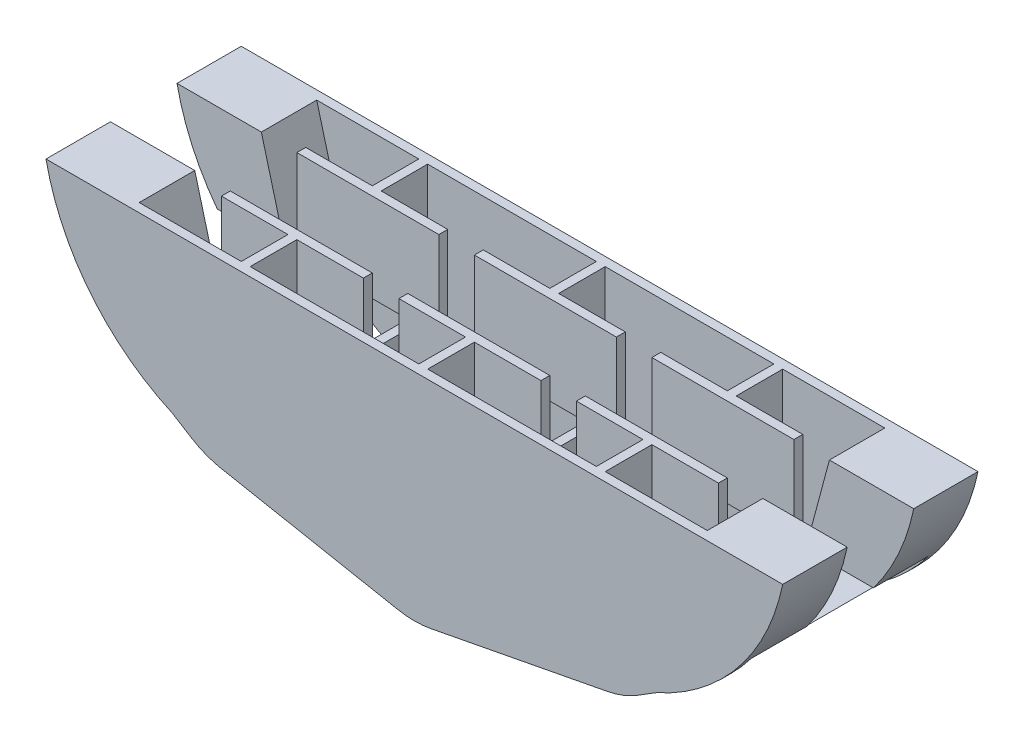
SolidWorks part; units mm, degrees
ref_plane "Front" through (0, 0, 0) normal (0, 0, 1) x (1, 0, 0)
ref_plane "Top" through (0, 0, 0) normal (0, 1, 0) x (1, 0, 0)
ref_plane "Right" through (0, 0, 0) normal (1, 0, 0) x (0, 0, -1)
sketch "Sketch1" plane through (0, 0, 0) normal (0, 0, 1) x (1, 0, 0)
  line L0 (-152.4, 62.23) -> (0, 62.23) construction
  line L1 (-152.4, -62.23) -> (152.4, -62.23) construction
  line L2 (-152.4, -62.23) -> (-152.4, 62.23) construction
  line L3 (-152.4, 62.23) -> (152.4, 62.23) construction
  line L4 (152.4, -62.23) -> (152.4, 62.23) construction
  line L5 (-152.4, -62.23) -> (152.4, 62.23) construction
  line L6 (-152.4, 62.23) -> (152.4, -62.23) construction
  line L7 (-152.4, 62.23) -> (-152.4, -33.02)
  line L8 (-152.4, -33.02) -> (0, -62.23)
  line L9 (0, -62.23) -> (152.4, -32.9764)
  line L10 (152.4, -32.9764) -> (152.4, 62.23)
  line L11 (152.4, 62.23) -> (-152.4, 62.23)
  point P0 (0, 0)
  dimension "D1" = 304.8
  dimension "D2" = 124.46
  dimension "D3" = 95.25
extrude "Boss-Extrude1" add sketch "Sketch1" against normal blind 111.76
ref_plane "Plane1" through (0, 0, -5.08) normal (0, 0, 1) x (1, 0, 0)
sketch "Sketch2" plane through (0, 0, 0) normal (0, 0, 1) x (1, 0, 0)
  line L0 (-152.4, -33.02) -> (-152.4, -13.97) construction
  line L1 (-152.4, 62.23) -> (-152.4, -33.02) construction
  line L2 (152.4, -32.9764) -> (152.4, 62.23) construction
  line L3 (-152.4, -13.97) -> (152.4, -13.97)
  line L4 (-152.4, -13.97) -> (-152.4, 11.43)
  line L5 (-152.4, 11.43) -> (152.4, 11.43)
  line L6 (152.4, -13.97) -> (152.4, 11.43)
  dimension "D1" = 19.05
  dimension "D2" = 25.4
sketch "Sketch5" plane through (0, 0, -5.08) normal (0, 0, 1) x (1, 0, 0)
  line L1 (-152.4, 11.43) -> (152.4, 11.43)
  line L2 (-152.4, 11.43) -> (-152.4, -13.97)
  line L3 (-152.4, -13.97) -> (152.4, -13.97)
  line L4 (152.4, 11.43) -> (152.4, -13.97)
  dimension "D1" = 19.05
  dimension "D2" = 25.4
extrude "Cut-Extrude3" cut sketch "Sketch5" against normal blind 101.6
sketch "Sketch3" plane through (0, 62.23, 0) normal (0, 1, 0) x (1, 0, 0)
  line L0 (152.4, 111.76) -> (-152.4, 111.76) construction
  line L1 (-2.54, 5.08) -> (-99.06, 5.08)
  line L2 (-2.54, 5.08) -> (-2.54, 106.68)
  line L3 (-2.54, 106.68) -> (-99.06, 106.68)
  line L4 (-99.06, 5.08) -> (-99.06, 106.68)
  line L5 (152.4, 0) -> (-152.4, 0) construction
  line L6 (0, 0) -> (0, 111.76) construction
  line L7 (2.54, 106.68) -> (99.06, 106.68)
  line L8 (99.06, 5.08) -> (99.06, 106.68)
  line L9 (2.54, 5.08) -> (99.06, 5.08)
  line L10 (2.54, 5.08) -> (2.54, 106.68)
  line L11 (-152.4, 111.76) -> (-152.4, 0) construction
  line L12 (-104.14, 106.68) -> (-152.4, 106.68)
  line L13 (-104.14, 106.68) -> (-104.14, 5.08)
  line L14 (-104.14, 5.08) -> (-152.4, 5.08)
  line L15 (-152.4, 106.68) -> (-152.4, 5.08)
  line L16 (104.14, 5.08) -> (152.4, 5.08)
  line L17 (152.4, 106.68) -> (152.4, 5.08)
  line L18 (104.14, 106.68) -> (152.4, 106.68)
  line L19 (104.14, 106.68) -> (104.14, 5.08)
  dimension "D1" = 2.54
  dimension "D2" = 96.52
  dimension "D3" = 5.08
  dimension "D4" = 5.08
  dimension "D5" = 5.08
  dimension "D6" = 5.08
  dimension "D7" = 5.08
extrude "Cut-Extrude4" cut sketch "Sketch3" against normal through all both and the other way through all
sketch "Sketch6" plane through (-104.14, 0, 0) normal (-1, 0, 0) x (0, 0, 1)
  line L0 (-5.08, 11.43) -> (-106.68, 11.43) construction
  line L1 (-74.9821, 11.43) -> (-36.8821, 11.43)
  line L2 (-74.9821, 11.43) -> (-74.9821, 62.23)
  line L3 (-74.9821, 62.23) -> (-36.8821, 62.23)
  line L4 (-36.8821, 11.43) -> (-36.8821, 62.23)
  line L5 (-5.08, 62.23) -> (-106.68, 62.23) construction
  dimension "D1" = 38.1
extrude "Cut-Extrude5" cut sketch "Sketch6" against normal up to surface (208.28 mm away) up to face at (104.14, 36.83, -55.88)
ref_plane "Plane2" through (0, 0, -36.8821) normal (0, 0, -1) x (-1, 0, 0)
sketch "Sketch7" plane through (0, 0, -36.8821) normal (0, 0, -1) x (-1, 0, 0)
  line L1 (-40.64, 62.23) -> (40.64, 62.23)
  line L2 (-40.64, 62.23) -> (-40.64, 11.43)
  line L3 (-40.64, 11.43) -> (40.64, 11.43)
  line L4 (40.64, 62.23) -> (40.64, 11.43)
  line L5 (60.96, 62.23) -> (142.24, 62.23)
  line L6 (60.96, 62.23) -> (60.96, 11.43)
  line L7 (60.96, 11.43) -> (142.24, 11.43)
  line L8 (142.24, 62.23) -> (142.24, 11.43)
  line L9 (-142.24, 62.23) -> (-60.96, 62.23)
  line L10 (-142.24, 62.23) -> (-142.24, 11.43)
  line L11 (-142.24, 11.43) -> (-60.96, 11.43)
  line L12 (-60.96, 62.23) -> (-60.96, 11.43)
  dimension "D1" = 38.1
  dimension "D2" = 38.1
  dimension "D3" = 38.1
  dimension "D4" = 38.1
  dimension "D5" = 38.1
  dimension "D6" = 38.1
extrude "Boss-Extrude2" add sketch "Sketch7" against normal blind 5.08
ref_plane "Plane3" through (0, 0, -55.9321) normal (0, 0, -1) x (-1, 0, 0)
mirror "Mirror1" about plane through (0, 0, -55.9321) normal (0, 0, -1) of "Boss-Extrude2"
sketch "Sketch8" plane through (0, 0, 0) normal (0, 0, 1) x (1, 0, 0)
  line L0 (152.4, 62.23) -> (-152.4, 62.23) construction
  circle A0 centre (50.8, 36.83) radius 10.16
  dimension "D1" = 20.32
  dimension "D2" = 25.4
  dimension "D3" = 50.8
sketch "Sketch9" plane through (-152.4, 0, 0) normal (-1, 0, 0) x (0, 0, 1)
  line L1 (-111.76, 62.23) -> (-106.68, 62.23)
  line L2 (-111.76, 62.23) -> (-111.76, -33.02)
  line L3 (-111.76, -33.02) -> (-106.68, -33.02)
  line L4 (-106.68, 62.23) -> (-106.68, -33.02)
  line L5 (-5.08, -33.02) -> (0, -33.02)
  line L6 (-5.08, -33.02) -> (-5.08, 62.23)
  line L7 (-5.08, 62.23) -> (0, 62.23)
  line L8 (0, -33.02) -> (0, 62.23)
extrude "Boss-Extrude3" add sketch "Sketch9" along normal blind 10.16
sketch "Sketch10" plane through (152.4, 0, 0) normal (1, 0, 0) x (0, 0, -1)
  line L1 (0, 62.23) -> (5.08, 62.23)
  line L2 (0, 62.23) -> (0, -32.9764)
  line L3 (0, -32.9764) -> (5.08, -32.9764)
  line L4 (5.08, 62.23) -> (5.08, -32.9764)
  line L5 (106.68, -32.9764) -> (111.76, -32.9764)
  line L6 (106.68, -32.9764) -> (106.68, 62.23)
  line L7 (106.68, 62.23) -> (111.76, 62.23)
  line L8 (111.76, -32.9764) -> (111.76, 62.23)
extrude "Boss-Extrude4" add sketch "Sketch10" along normal blind 10.16
sketch "Sketch11" plane through (0, 0, 0) normal (0, 0, 1) x (1, 0, 0)
  line L0 (-162.56, -12.7) -> (-119.6963, -39.2882)
  line L1 (-162.56, -33.02) -> (-162.56, 62.23) construction
  line L2 (-152.4, -33.02) -> (0, -62.23) construction
  line L3 (-119.6963, -39.2882) -> (-152.4, -33.02)
  line L4 (-152.4, -33.02) -> (-162.56, -33.02)
  line L5 (-162.56, -33.02) -> (-162.56, -12.7)
  line L6 (0, -75.9725) -> (0, 75.9725) construction
  line L7 (152.4, -33.02) -> (162.56, -33.02)
  line L8 (119.6963, -39.2882) -> (152.4, -33.02)
  line L9 (162.56, -12.7) -> (119.6963, -39.2882)
  line L10 (162.56, -33.02) -> (162.56, -12.7)
  dimension "D1" = 20.32
extrude "Cut-Extrude7" cut sketch "Sketch11" against normal up to surface (111.76 mm away) up to face at (0, -9.9661, -111.76)
fillet "Fillet1" radius 50.8 9 edges at (-162.56, -12.7, -2.54) (-162.56, -12.7, -109.22) (-119.6963, -39.2882, -109.22) (-119.6963, -39.2882, -2.54) (162.56, -12.7, -109.22) (162.56, -12.7, -2.54) (119.7762, -39.2387, -109.22) (119.7762, -39.2387, -2.54) (0, -62.23, -55.88)
sketch "Sketch12" plane through (0, 0, 0) normal (0, 0, 1) x (1, 0, 0)
  line L0 (-162.56, 62.23) -> (-210.82, 62.23)
  line L1 (-162.56, 62.23) -> (-138.5378, -27.6009)
  line L2 (0, -75.9725) -> (0, 75.9725) construction
  line L3 (162.56, 62.23) -> (210.82, 62.23)
  line L4 (162.56, 62.23) -> (138.5378, -27.6009)
  arc A0 (-138.5378, -27.6009) -> (-210.82, 62.23) centre (-87.1093, 87.7772) cw
  arc A1 (138.5378, -27.6009) -> (210.82, 62.23) centre (87.1093, 87.7772) ccw
  dimension "D1" = 48.26
extrude "Boss-Extrude5" add sketch "Sketch12" against normal up to surface (111.76 mm away) up to face at (0.0134, -14.9837, -111.76)
sketch "Sketch13" plane through (0, 0, 0) normal (1, 0, 0) x (0, 0, -1)
  line L0 (36.8821, 62.23) -> (36.8821, 11.43)
  line L1 (36.8821, 11.43) -> (5.08, 11.43)
  line L2 (5.08, 11.43) -> (5.08, -13.97)
  line L3 (5.08, -13.97) -> (106.68, -13.97)
  line L4 (106.68, -13.97) -> (106.68, 11.43)
  line L5 (106.68, 11.43) -> (74.9821, 11.43)
  line L6 (74.9821, 11.43) -> (74.9821, 62.23)
  line L7 (74.9821, 62.23) -> (36.8821, 62.23)
extrude "Cut-Extrude8" cut sketch "Sketch13" against normal up to surface and the other way up to surface up to face at (-166.2475, -0.5666, -55.88) other way up to face at (166.2475, -0.5666, -55.88)
